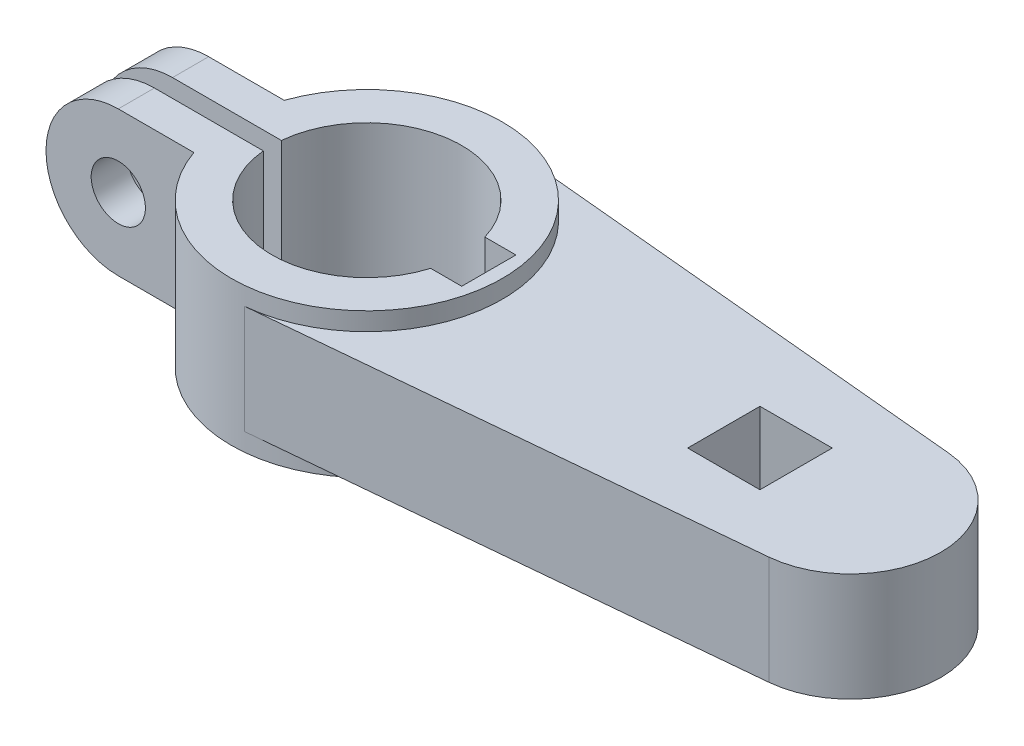
SolidWorks part; units mm, degrees
ref_plane "Front Plane" through (0, 0, 0) normal (0, 0, 1) x (1, 0, 0)
ref_plane "Top Plane" through (0, 0, 0) normal (0, 1, 0) x (1, 0, 0)
ref_plane "Right Plane" through (0, 0, 0) normal (1, 0, 0) x (0, 0, -1)
sketch "Sketch1" plane through (0, 0, 0) normal (0, 1, 0) x (1, 0, 0)
  line L0 (54.4346, 9.9562) -> (1.4019, 14.9343)
  line L4 (-30.5, -5) -> (-30.5, -1)
  line L5 (54.4346, -9.9562) -> (1.4019, -14.9343)
  line L6 (10.0623, 3) -> (13.5, 3)
  line L7 (-14.1421, -5) -> (-30.5, -5)
  line L11 (-14.1421, 5) -> (-30.5, 5)
  line L12 (13.5, -3) -> (13.5, 3)
  line L15 (-30.5, 1) -> (-30.5, 5)
  line L16 (10.0623, -3) -> (13.5, -3)
  line L17 (-10.4523, 1) -> (-30.5, 1)
  line L18 (-10.4523, -1) -> (-30.5, -1)
  arc A0 (-10.4523, -1) -> (10.0623, -3) centre (0, 0) ccw
  arc A1 (-14.1421, -5) -> (-14.1421, 5) centre (0, 0) ccw
  arc A3 (54.4346, -9.9562) -> (54.4346, 9.9562) centre (53.5, 0) ccw
  arc A4 (10.0623, 3) -> (-10.4523, 1) centre (0, 0) ccw
extrude "Boss-Extrude1" add sketch "Sketch1" along normal mid plane 16 contours A4 L6 L12 L16 A0 L18 L4 L7 A1 L11 L15 L17 region at (14.455, 0, 0)
extrude "Boss-Extrude2" add sketch "Sketch1<4>" along normal mid plane 12 contours L5 A3 L0 A1 region at (35.189, 0, 0)
sketch "Sketch1<4>" plane through (0, 0, 0) normal (0, 1, 0) x (1, 0, 0) same geometry as "Sketch1"
sketch "Sketch2" plane through (0, 0, 5) normal (0, 0, 1) x (1, 0, 0)
  line L1 (-22.5, 8) -> (-22.5, 10.6435)
  line L2 (-22.5, 10.6435) -> (-32.2669, 10.6435)
  line L3 (-32.2669, 10.6435) -> (-32.2669, -8)
  line L4 (-32.2669, -8) -> (-32.2669, -9.0486)
  line L5 (-22.5, -8) -> (-22.5, -9.0486)
  line L6 (-22.5, -9.0486) -> (-32.2669, -9.0486)
  arc A1 (-22.5, 8) -> (-22.5, -8) centre (-22.5, 0) ccw
  circle A2 centre (-22.5, 0) radius 3
extrude "Cut-Extrude2" cut sketch "Sketch2" against normal blind 12
sketch "Sketch3" plane through (0, 6, 0) normal (0, 1, 0) x (1, 0, 0)
  line L3 (39.5, -4) -> (47.5, -4)
  line L4 (39.5, -4) -> (39.5, 4)
  line L5 (39.5, 4) -> (47.5, 4)
  line L6 (47.5, -4) -> (47.5, 4)
  line L7 (39.5, -4) -> (47.5, 4) construction
  line L8 (39.5, 4) -> (47.5, -4) construction
sketch "Sketch4" plane through (0, -6, 0) normal (0, -1, 0) x (1, 0, 0)
  line L0 (39.5, 4) -> (47.5, -4) construction
  line L1 (38.5, -5) -> (48.5, -5)
  line L2 (38.5, -5) -> (38.5, 5)
  line L3 (38.5, 5) -> (48.5, 5)
  line L4 (48.5, -5) -> (48.5, 5)
  line L5 (38.5, -5) -> (48.5, 5) construction
  line L6 (38.5, 5) -> (48.5, -5) construction
  point P0 (43.5, 0)
loft "Cut-Loft1" cut profiles "Sketch4", "Sketch3" connector at (38.5, -6, 5) connector at (39.5, 6, 4)
